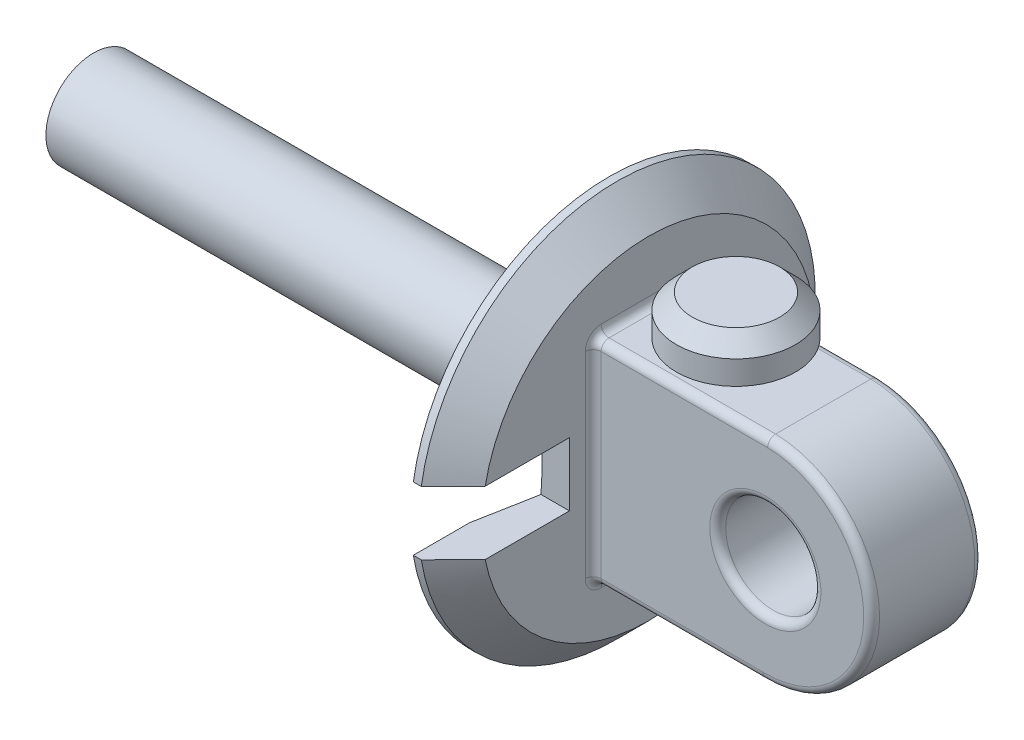
SolidWorks part; units mm, degrees
ref_plane "Front Plane" through (0, 0, 0) normal (0, 0, 1) x (1, 0, 0)
ref_plane "Top Plane" through (0, 0, 0) normal (0, 1, 0) x (1, 0, 0)
ref_plane "Right Plane" through (0, 0, 0) normal (1, 0, 0) x (0, 0, -1)
sketch "Sketch1" plane through (0, 0, 0) normal (0, 0, 1) x (1, 0, 0)
  line L0 (0.2977, 13.3967) -> (-21.7023, 13.3967)
  line L1 (-0.2977, -13.3967) -> (-21.7023, -13.3967)
  line L2 (-21.7023, -13.3967) -> (-21.7023, 13.3967)
  circle A0 centre (0, 0) radius 6
  arc A1 (0.2977, 13.3967) -> (-0.2977, -13.3967) centre (0, 0) cw
  dimension "D1" = 12
  dimension "D2" = 13.4
  dimension "D3" = 22
extrude "Boss-Extrude1" add sketch "Sketch1" along normal mid plane 14
sketch "Sketch2" plane through (-21.7023, 0, 0) normal (-1, 0, 0) x (0, 0, 1)
  circle A0 centre (0, 0) radius 25
  dimension "D1" = 50
extrude "Boss-Extrude2" add sketch "Sketch2" along normal blind 5
sketch "Sketch3" plane through (0, 0, 0) normal (0, 0, 1) x (1, 0, 0)
  line L0 (-26.7023, 0) -> (-23.2023, 0)
  line L1 (-26.7023, 25) -> (-26.7023, -25) construction
  line L2 (-23.2023, 0) -> (-26.7023, -18)
  line L3 (-26.7023, 0) -> (-26.7023, -18)
  dimension "D1" = 18
  dimension "D2" = 3.5
revolve "Cut-Revolve2" cut sketch "Sketch3" angle 360 about L0
chamfer "Chamfer1" distance 4 angle 45 1 edges at (-21.7023, 0, 25)
sketch "Sketch4" plane through (-21.7023, 0, 0) normal (1, 0, 0) x (0, 0, -1)
  circle A0 centre (0, 0) radius 6
  dimension "D1" = 12
extrude "Boss-Extrude3" add sketch "Sketch4" against normal blind 70
sketch "Sketch5" plane through (0, 13.3967, 0) normal (0, 1, 0) x (1, 0, 0)
  circle A0 centre (-10.7023, 0) radius 3
  dimension "D1" = 6
extrude "Boss-Extrude4" add sketch "Sketch5" along normal blind 2
sketch "Sketch6" plane through (0, 15.3967, 0) normal (0, 1, 0) x (1, 0, 0)
  circle A0 centre (-10.7023, 0) radius 7.5
  dimension "D1" = 15
extrude "Boss-Extrude5" add sketch "Sketch6" along normal blind 5
chamfer "Chamfer2" distance 2 angle 45 1 edges at (-18.2023, 20.3967, 0)
sketch "Sketch7" plane through (-26.7023, 0, 0) normal (-1, 0, 0) x (0, 0, 1)
  line L1 (10, 4) -> (40, 4)
  line L2 (10, 4) -> (10, -4)
  line L3 (10, -4) -> (40, -4)
  line L4 (40, 4) -> (40, -4)
  line L5 (10, 4) -> (40, -4) construction
  line L6 (10, -4) -> (40, 4) construction
  circle A0 centre (0, 0) radius 25 construction
  point P0 (25, 0)
  dimension "D1" = 30
  dimension "D2" = 8
extrude "Cut-Extrude1" cut sketch "Sketch7" against normal through all both and the other way through all
fillet "Fillet1" radius 1 12 edges at (-21.7023, -13.3967, 0) (-21.7023, 13.3967, 0) (6, 0, -7) (-10.7023, 13.3967, -7) (-21.7023, 0, -7) (-11, -13.3967, -7) (13.3967, -0.2977, -7) (6, 0, 7) (-11, -13.3967, 7) (-21.7023, 0, 7) (-10.7023, 13.3967, 7) (13.3967, -0.2977, 7)
